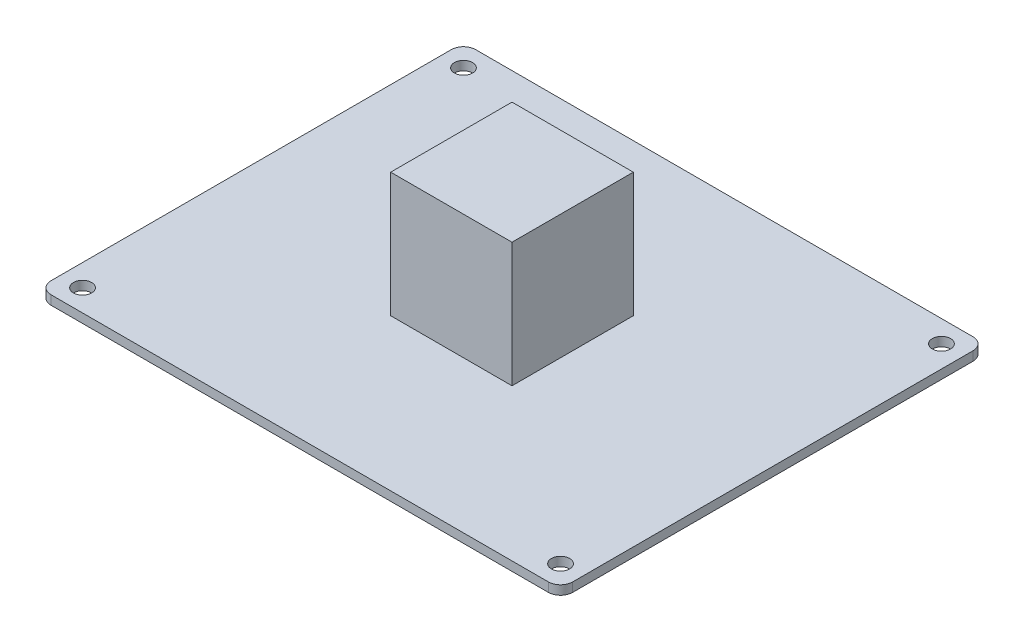
SolidWorks part; units mm, degrees
material "ABS"
ref_plane "Front Plane" through (0, 0, 0) normal (0, 0, 1) x (1, 0, 0)
ref_plane "Top Plane" through (0, 0, 0) normal (0, 1, 0) x (1, 0, 0)
ref_plane "Right Plane" through (0, 0, 0) normal (1, 0, 0) x (0, 0, -1)
sketch "Sketch1" plane through (0, 0, 0) normal (0, 1, 0) x (1, 0, 0)
  line L1 (-43, -35) -> (43, -35)
  line L2 (-43, -35) -> (-43, 35)
  line L3 (-43, 35) -> (43, 35)
  line L4 (43, -35) -> (43, 35)
  line L5 (-43, -35) -> (43, 35) construction
  line L6 (-43, 35) -> (43, -35) construction
  point P0 (0, 0)
  dimension "D1" = 86
  dimension "D2" = 70
extrude "Boss-Extrude1" add sketch "Sketch1" along normal blind 1.5
fillet "Fillet1" radius 2 4 edges at (-43, 0.75, 35) (-43, 0.75, -35) (43, 0.75, -35) (43, 0.75, 35)
sketch "Sketch2" plane through (0, 0, 0) normal (0, -1, 0) x (1, 0, 0)
  line L1 (10, -10) -> (-10, -10)
  line L2 (10, -10) -> (10, 10)
  line L3 (10, 10) -> (-10, 10)
  line L4 (-10, -10) -> (-10, 10)
  line L5 (10, -10) -> (-10, 10) construction
  line L6 (10, 10) -> (-10, -10) construction
  point P0 (0, 0)
  dimension "D1" = 20
  dimension "D2" = 20
extrude "Boss-Extrude2" add sketch "Sketch2" against normal blind 22
hole_wizard "Ø1.0mm Dowel Hole1" positions "3DSketch1" profile "Sketch3" hole size "Ø1.0" standard "ANSI Metric" end condition through all
sketch3d "3DSketch1"
  line L0 (41, 1.5, -35) -> (-41, 1.5, -35) construction
  line L1 (-43, 1.5, -33) -> (-43, 1.5, 33) construction
  line L2 (-41, 1.5, 35) -> (41, 1.5, 35) construction
  line L3 (43, 1.5, 33) -> (43, 1.5, -33) construction
  point P0 (-39.4, 1.5, -31.4)
  point P2 (39.4, 1.5, -31.4)
  point P4 (-39.4, 1.5, 31.4)
  point P6 (39.4, 1.5, 31.4)
  dimension "D1" = 3.6
  dimension "D2" = 3.6
  dimension "D3" = 3.6
  dimension "D4" = 3.6
  dimension "D5" = 3.6
  dimension "D6" = 3.6
  dimension "D7" = 3.6
  dimension "D8" = 3.6
sketch "Sketch3" plane through (-39.4, 1.5, -31.4) normal (1, 0, 0) x (0, 0, 1)
  line L0 (0, 0) -> (0, 1.5)
  line L1 (0, 1.5) -> (1.5, 1.5)
  line L2 (1.5, 1.5) -> (1.5, 0)
  line L5 (1.5, 0) -> (0, 0)
  line L11 (0, -6.35) -> (0, 107.95) construction
  dimension "Thru Hole Dia." = 3
  dimension "Thru Hole Depth" = 1.5
